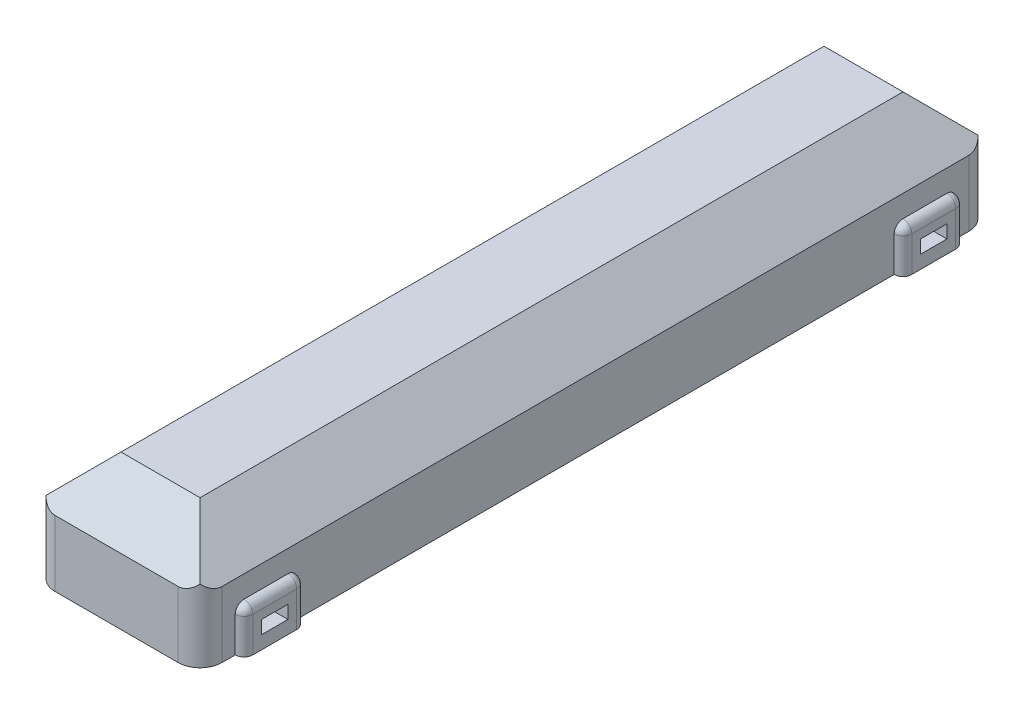
SolidWorks part; units mm, degrees
ref_plane "Front Plane" through (0, 0, 0) normal (0, 0, 1) x (1, 0, 0)
ref_plane "Top Plane" through (0, 0, 0) normal (0, 1, 0) x (1, 0, 0)
ref_plane "Right Plane" through (0, 0, 0) normal (1, 0, 0) x (0, 0, -1)
sketch "Sketch1" plane through (0, 0, 0) normal (0, 1, 0) x (1, 0, 0)
  line L1 (-19, -90) -> (19, -90)
  line L2 (-19, -90) -> (-19, 90)
  line L3 (-19, 90) -> (19, 90)
  line L4 (19, -90) -> (19, 90)
  line L5 (-19, -90) -> (19, 90) construction
  line L6 (-19, 90) -> (19, -90) construction
  point P0 (0, 0)
  dimension "D1" = 180
  dimension "D2" = 38
extrude "Boss-Extrude1" add sketch "Sketch1" along normal blind 25
sketch "Sketch2" plane through (0, 0, 0) normal (0, -1, 0) x (1, 0, 0)
  line L1 (-16, -87) -> (16, -87)
  line L2 (-16, -87) -> (-16, 87)
  line L3 (-16, 87) -> (16, 87)
  line L4 (16, -87) -> (16, 87)
  line L5 (-16, -87) -> (16, 87) construction
  line L6 (-16, 87) -> (16, -87) construction
  point P0 (0, 0)
  dimension "D1" = 32
  dimension "D2" = 174
extrude "Cut-Extrude1" cut sketch "Sketch2" against normal blind 22
chamfer "Chamfer1" distance 10 angle 45 8 edges at (0, 25, 90) (-19, 25, 0) (19, 25, 0) (0, 25, -90) (0, 22, -87) (-16, 22, 0) (0, 22, 87) (16, 22, 0)
fillet "Fillet1" radius 5 4 edges at (-19, 7.5, -90) (19, 7.5, -90) (-19, 7.5, 90) (19, 7.5, 90)
fillet "Fillet2" radius 2 4 edges at (-16, 6, -87) (16, 6, -87) (16, 6, 87) (-16, 6, 87)
sketch "Sketch3" plane through (19, 0, 0) normal (1, 0, 0) x (0, 0, -1)
  line L0 (-85, 0) -> (85, 0) construction
  line L1 (-68, 10) -> (-82, 10)
  line L2 (-68, 10) -> (-68, 0)
  line L3 (-68, 0) -> (-82, 0)
  line L4 (-82, 10) -> (-82, 0)
  line L5 (-68, 10) -> (-82, 0) construction
  line L6 (-68, 0) -> (-82, 10) construction
  line L7 (-85, 15) -> (-85, 0) construction
  line L8 (0, 0) -> (0, 15) construction
  line L9 (85, 15) -> (-85, 15) construction
  line L10 (68, 0) -> (82, 0)
  line L11 (82, 10) -> (82, 0)
  line L12 (68, 0) -> (82, 10) construction
  line L13 (68, 10) -> (82, 0) construction
  line L14 (68, 10) -> (68, 0)
  line L15 (68, 10) -> (82, 10)
  point P0 (-75, 5)
  point P18 (75, 5)
  dimension "D1" = 3
  dimension "D2" = 14
  dimension "D3" = 10
extrude "Boss-Extrude2" add sketch "Sketch3" along normal blind 2
sketch "Sketch4" plane through (-19, 0, 0) normal (-1, 0, 0) x (0, 0, 1)
  line L0 (-85, 0) -> (85, 0) construction
  line L1 (-68, 10.9395) -> (-82, 10.9395)
  line L2 (-68, 10.9395) -> (-68, 0)
  line L3 (-68, 0) -> (-82, 0)
  line L4 (-82, 10.9395) -> (-82, 0)
  line L5 (-68, 10.9395) -> (-82, 0) construction
  line L6 (-68, 0) -> (-82, 10.9395) construction
  line L7 (-85, 15) -> (-85, 0) construction
  line L8 (0, 15) -> (0, 0) construction
  line L9 (85, 15) -> (-85, 15) construction
  line L10 (68, 0) -> (82, 10.9395) construction
  line L11 (68, 10.9395) -> (82, 0) construction
  line L12 (82, 10.9395) -> (82, 0)
  line L13 (68, 0) -> (82, 0)
  line L14 (68, 10.9395) -> (68, 0)
  line L15 (68, 10.9395) -> (82, 10.9395)
  point P0 (-75, 5.4697)
  point P18 (75, 5.4697)
  dimension "D1" = 3
  dimension "D2" = 14
  dimension "D3" = 10.9395
extrude "Boss-Extrude3" add sketch "Sketch4" along normal blind 2
sketch "Sketch5" plane through (-21, 0, 0) normal (-1, 0, 0) x (0, 0, 1)
  line L0 (-82, 10.9395) -> (-82, 0) construction
  line L1 (-72, 3) -> (-78, 3)
  line L2 (-72, 3) -> (-72, 6)
  line L3 (-72, 6) -> (-78, 6)
  line L4 (-78, 3) -> (-78, 6)
  line L5 (-72, 3) -> (-78, 6) construction
  line L6 (-72, 6) -> (-78, 3) construction
  line L7 (-82, 0) -> (-68, 0) construction
  line L8 (0, 15) -> (0, 0) construction
  line L9 (85, 15) -> (-85, 15) construction
  line L10 (72, 6) -> (78, 3) construction
  line L11 (72, 3) -> (78, 6) construction
  line L12 (78, 3) -> (78, 6)
  line L13 (72, 6) -> (78, 6)
  line L14 (72, 3) -> (72, 6)
  line L15 (72, 3) -> (78, 3)
  point P0 (-75, 4.5)
  point P19 (75, 4.5)
  dimension "D1" = 6
  dimension "D2" = 3
  dimension "D3" = 4
  dimension "D4" = 3
extrude "Cut-Extrude2" cut sketch "Sketch5" against normal through all both and the other way through all
fillet "Fillet3" radius 2 12 edges at (-21, 5.4697, 82) (-21, 10.9395, 75) (-21, 5.4697, 68) (-21, 5.4697, -68) (-21, 10.9395, -75) (-21, 5.4697, -82) (21, 10, -75) (21, 5, -82) (21, 5, -68) (21, 5, 68) (21, 10, 75) (21, 5, 82)
